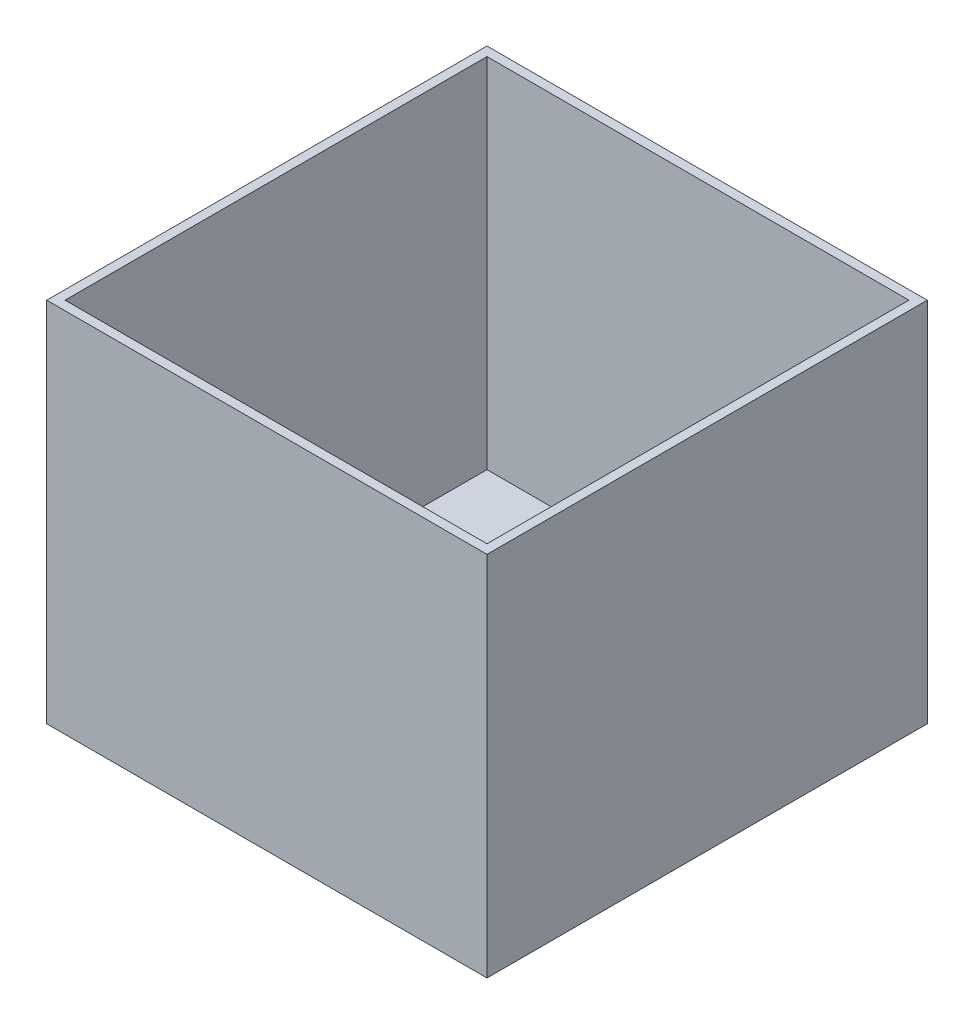
SolidWorks part; units mm, degrees
ref_plane "Front Plane" through (0, 0, 0) normal (0, 0, 1) x (1, 0, 0)
ref_plane "Top Plane" through (0, 0, 0) normal (0, 1, 0) x (1, 0, 0)
ref_plane "Right Plane" through (0, 0, 0) normal (1, 0, 0) x (0, 0, -1)
sketch "Sketch2" plane through (0, -113.102, 0) normal (0, 1, 0) x (1, 0, 0)
  line L1 (-120, -120) -> (120, -120)
  line L2 (-120, -120) -> (-120, 120)
  line L3 (-120, 120) -> (120, 120)
  line L4 (120, -120) -> (120, 120)
  line L5 (-120, -120) -> (120, 120) construction
  line L6 (-120, 120) -> (120, -120) construction
  point P0 (0, 0)
  dimension "D1" = 240
  dimension "D2" = 240
extrude "Boss-Extrude1" add sketch "Sketch2" along normal blind 200
sketch "Sketch17" plane through (0, 86.898, 0) normal (0, 1, 0) x (1, 0, 0)
  line L0 (-115, -115) -> (-115, 115)
  line L1 (-115, 115) -> (115, 115)
  line L2 (115, 115) -> (115, -115)
  line L3 (115, -115) -> (-115, -115)
  line L4 (-120, -120) -> (120, -120) construction
  line L6 (-120, 120) -> (-120, -120) construction
  point P4 (-115, 0)
  dimension "D1" = 230
  dimension "D2" = 5
  dimension "D3" = 230
  dimension "D4" = 5
extrude "Cut-Extrude1" cut sketch "Sketch17" against normal blind 195
